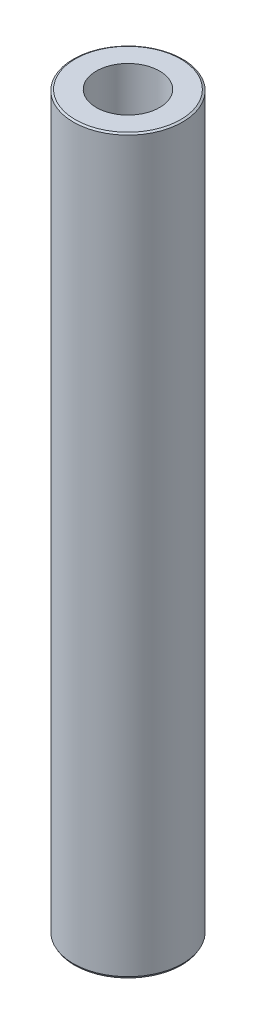
SolidWorks part; units mm, degrees
ref_plane "Front Plane" through (0, 0, 0) normal (0, 0, 1) x (1, 0, 0)
ref_plane "Top Plane" through (0, 0, 0) normal (0, 1, 0) x (1, 0, 0)
ref_plane "Right Plane" through (0, 0, 0) normal (1, 0, 0) x (0, 0, -1)
sketch "Sketch1" plane through (0, 0, 0) normal (0, 1, 0) x (1, 0, 0)
  circle A0 centre (0, 0) radius 40
  dimension "SHAFT_OD" = 80
extrude "Boss-Extrude1" add sketch "Sketch1" along normal blind 536.2005
sketch "Sketch2" plane through (0, 0, 0) normal (0, 1, 0) x (1, 0, 0)
  circle A0 centre (0, 0) radius 23.1925
  dimension "BORE_D" = 46.3849
extrude "Cut-Extrude1" cut sketch "Sketch2" along normal through all
chamfer "Chamfer1" distance 0.8264 angle 60 2 edges at (0, 536.2005, 40) (0, 0, 40) first distance on face at (0, 536.2005, 40) first distance on face at (0, 0, 23.1925)
